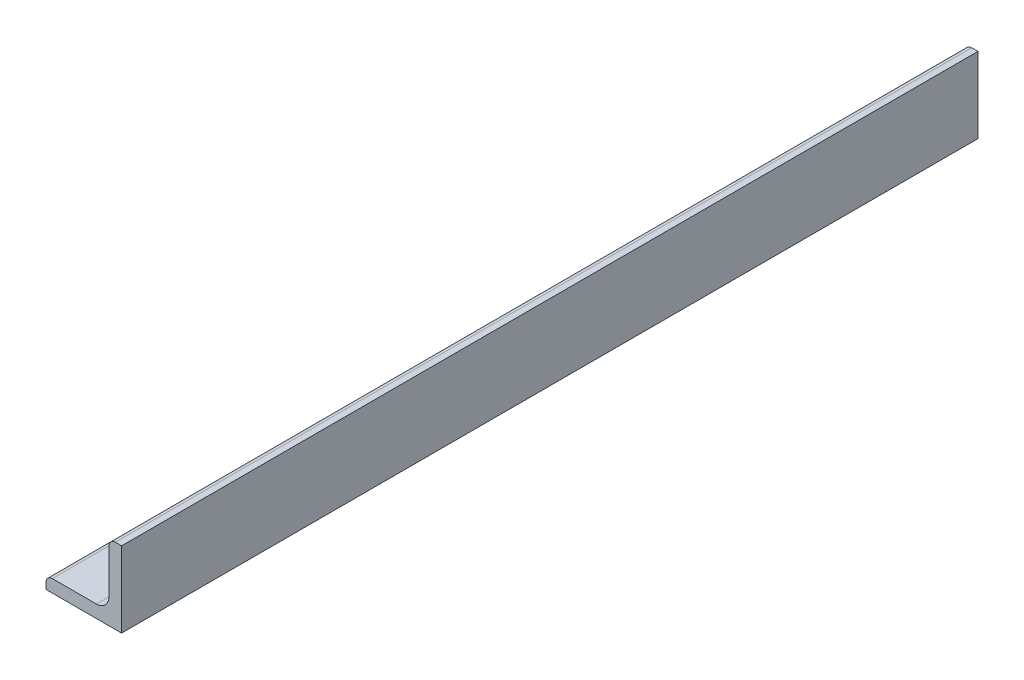
SolidWorks part; units mm, degrees
ref_plane "Front Plane" through (0, 0, 0) normal (0, 0, 1) x (1, 0, 0)
ref_plane "Top Plane" through (0, 0, 0) normal (0, 1, 0) x (1, 0, 0)
ref_plane "Right Plane" through (0, 0, 0) normal (1, 0, 0) x (0, 0, -1)
sketch "Sketch2" plane through (0, 0, 0) normal (0, 0, 1) x (1, 0, 0)
  line L0 (-9.525, 0) -> (9.525, 0)
  line L1 (9.525, 0) -> (9.525, 19.05)
  line L2 (9.525, 19.05) -> (6.35, 19.05) construction
  line L3 (6.35, 17.4625) -> (6.35, 6.35)
  line L4 (3.175, 3.175) -> (-7.9375, 3.175)
  line L5 (-9.525, 0) -> (-9.525, 3.175) construction
  line L6 (7.9375, 19.05) -> (9.525, 19.05)
  line L7 (-9.525, 1.5875) -> (-9.525, 0)
  arc A0 (6.35, 17.4625) -> (7.9375, 19.05) centre (7.9375, 17.4625) cw
  arc A1 (-9.525, 1.5875) -> (-7.9375, 3.175) centre (-7.9375, 1.5875) cw
  arc A2 (6.35, 6.35) -> (3.175, 3.175) centre (3.175, 6.35) cw
  dimension "Inside Radius" = 3.175
  dimension "Vert" = 19.05
  dimension "Horz" = 19.05
  dimension "Thickness" = 3.175
extrude "Boss-Extrude1" add sketch "Sketch2" along normal mid plane 215.9
sketch "Break Locations" plane through (0, 0, 0) normal (1, 0, 0) x (0, 0, -1)
  line L1 (-107.95, 0) -> (-107.95, 19.05) construction
  line L2 (107.95, 0) -> (107.95, 19.05) construction
  point P0 (-91.7575, 0)
  point P1 (91.7575, 0)
  dimension "D1" = 16.1925
  dimension "D2" = 16.1925
ref_plane "Contact Plane 1" through (0, 3.175, 0) normal (0, 1, 0) x (1, 0, 0)
ref_plane "Contact Plane 2" through (6.35, 0, 0) normal (-1, 0, 0) x (0, 0, 1)
sketch "Sketch3" plane through (0, 3.175, 0) normal (0, 1, 0) x (1, 0, 0)
  point P0 (-0.2937, 95.25)
  point P1 (-0.2937, -95.25)
hole_wizard "#6-32 Tapped Hole1" positions "Sketch4" profile "Sketch6" tap size "#6-32" standard "ANSI Inch" end condition through all
sketch "Sketch4" plane through (0, 3.175, 0) normal (0, 1, 0) x (1, 0, 0)
  point P0 (-0.2937, -95.25)
  point P3 (-0.2937, 95.25)
sketch "Sketch6" plane through (-0.2937, 3.175, 95.25) normal (1, 0, 0) x (0, 0, 1)
  line L0 (0, 0) -> (0, 3.175)
  line L1 (0, 3.175) -> (1.3525, 3.175)
  line L2 (1.3525, 3.175) -> (1.3525, 0)
  line L5 (1.3525, 0) -> (0, 0)
  line L11 (0, -6.35) -> (0, 107.95) construction
  dimension "Thru Tap Drill Dia." = 2.7051
  dimension "Thru Tap Drill Depth" = 3.175
cosmetic thread "Hole Thread4" parameters "D1"=7.112, "D2"=3.7051
cosmetic thread "Hole Thread5" parameters "D1"=7.112, "D2"=3.7051
equation "\"D1@Break Locations\"=.85*\"Vert@Sketch2\""
equation "\"D2@Break Locations\"=\"D1@Break Locations\""
